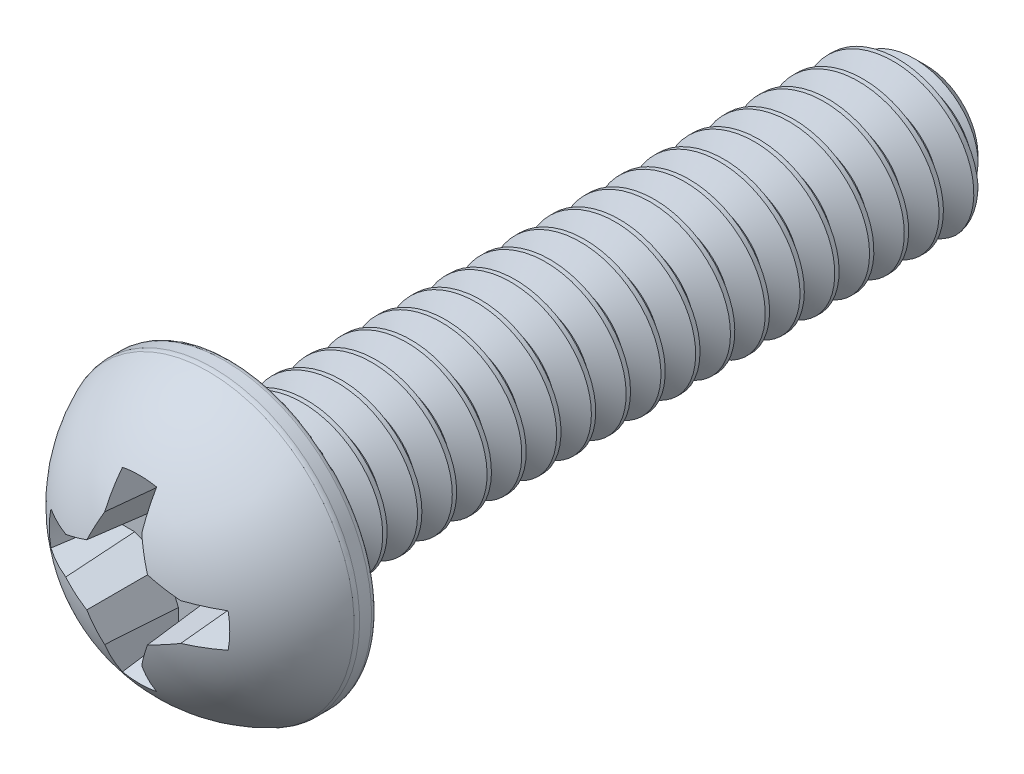
SolidWorks part; units mm, degrees
ref_plane "Front" through (0, 0, 0) normal (0, 0, 1) x (1, 0, 0)
ref_plane "Top" through (0, 0, 0) normal (0, 1, 0) x (1, 0, 0)
ref_plane "Right" through (0, 0, 0) normal (1, 0, 0) x (0, 0, -1)
sketch "Sketch1" plane through (0, 0, 0) normal (0, 0, 1) x (1, 0, 0)
  circle A0 centre (0, 0) radius 2.6797
  dimension "Head Dia" = 5.3594
extrude "Extrude3" add sketch "Sketch1" along normal blind 2.1844
sketch "Sketch11" plane through (0, 0, 0) normal (1, 0, 0) x (0, 0, -1)
  line L0 (0, 0) -> (-2.4384, 0) construction
  line L4 (-2.1844, 2.6797) -> (-2.1844, -2.6797) construction
  line L5 (-2.4384, 3.1064) -> (0, 3.1064)
  line L7 (0, 3.1064) -> (0, 2.5705)
  line L8 (-0.3277, 2.6797) -> (-0.1092, 2.6797)
  line L9 (0, -2.6797) -> (0, 2.6797) construction
  line L11 (0, 2.6797) -> (-2.1844, 2.6797) construction
  line L13 (-2.1844, 0) -> (-2.4384, 0)
  line L14 (-2.4384, 0) -> (-2.4384, 3.1064)
  arc A0 (-0.412, 2.6628) -> (-2.1844, 0) centre (0.702, 0) ccw
  arc A1 (-0.1092, 2.6797) -> (0, 2.5705) centre (-0.1092, 2.5705) cw
  arc A2 (-0.412, 2.6628) -> (-0.3277, 2.6797) centre (-0.3277, 2.4613) cw
  dimension "D2" = 0.1092
  dimension "D4" = 0.2184
  dimension "D3" = 0.254
  dimension "D1" = 0.2184
  dimension "D5" = 0.5359
revolve "Cut-Revolve3" cut sketch "Sketch11" angle 360 about L0
sketch "Sketch4" plane through (0, 0, 0) normal (1, 0, 0) x (0, 0, -1)
  line L0 (0, 0) -> (12.7, 0)
  line L3 (12.7, 0) -> (12.7, 1.4224)
  line L4 (12.7, 1.4224) -> (0, 1.4224)
  line L6 (0, 1.4224) -> (0, 0)
  line L9 (12.7, 1.4224) -> (12.7, -1.4224) construction
  dimension "length" = 12.7
  dimension "dia" = 2.8448
revolve "Revolve1" add sketch "Sketch4" angle 360 about L0
chamfer "Chamfer1" distance 0.4763 angle 45 1 edges at (1.4224, 0, -12.7)
sketch "Sketch13" plane through (0, 0, -12.7) normal (0, 0, -1) x (-1, 0, 0)
  circle A2 centre (0, 0) radius 1.4224
curve "Helix/Spiral1" pitch 0.635 height 14.605 turns 23
sketch "Sketch14" plane through (0, 0, 0) normal (1, 0, 0) x (0, 0, -1)
  line L0 (12.7, 1.4224) -> (13.2556, 1.4224)
  line L1 (13.2556, 1.4224) -> (13.0175, 0.9928)
  line L2 (13.0175, 0.9928) -> (12.9381, 0.9928)
  line L3 (12.9381, 0.9928) -> (12.7, 1.4224)
  line L4 (12.8191, 1.2076) -> (13.1366, 1.2076) construction
  dimension "D1" = 0.0794
  dimension "D2" = 58
  dimension "D3" = 0.3175
sweep "Cut-Sweep1" cut profiles "Sketch14" path "Helix/Spiral1"
ref_plane "Plane1" through (0, 0, 25.4) normal (0, 0, -1) x (-1, 0, 0)
sketch "Sketch29" [suppressed] plane through (0, 0, -38.1) normal (0, 0, -1) x (-1, 0, 0)
  circle A0 centre (0, 0) radius 4.7625 construction
  circle A1 centre (0, 0) radius 4.7625
  point P3 (0, -4.7625)
extrude "Extrude11" [suppressed] add sketch "Sketch29" against normal up to surface (38.1 mm away)
sketch "Sketch26" plane through (0, 0, 0) normal (0, 0, 1) x (1, 0, 0)
  circle A1 centre (0, 0) radius 0.5461
  dimension "D1" = 1.0922
extrude "Extrude8" add sketch "Sketch26" along normal up to surface (2.1323 mm away)
ref_plane "Plane2" through (0, 0, 2.1844) normal (0, 0, 1) x (1, 0, 0)
sketch "Sketch12" plane through (0, 0, 2.1844) normal (0, 0, 1) x (1, 0, 0)
  line L0 (0, 0) -> (0.3573, 0.3573) construction
  line L1 (0, 0) -> (0, -1.1128) construction
  line L2 (1.7504, 0.3573) -> (1.0538, 0.3573)
  line L3 (0, 1.7865) -> (0, 2.6797) construction
  line L8 (0.3573, 1.0538) -> (0.3573, 1.7504)
  line L9 (0.3573, 0.3573) -> (1.0538, 1.0538) construction
  line L10 (1.0538, 0.3573) -> (0.5613, 0.5613)
  line L11 (0.5613, 0.5613) -> (0.3573, 1.0538)
  line L12 (1.0538, 0.3573) -> (0.3573, 0.3573) construction
  line L13 (0.3573, 1.0538) -> (0.3573, 0.3573) construction
  line L14 (0, 0) -> (0, 1.7865)
  line L15 (0, 0) -> (1.7865, 0)
  circle A1 centre (0, 0) radius 2.6797 construction
  arc A2 (1.7865, 0) -> (1.7504, 0.3573) centre (0, 0) ccw
  arc A3 (0.3573, 1.7504) -> (0, 1.7865) centre (0, 0) ccw
  circle A5 centre (0, 0) radius 1.1128 construction
  arc A6 (1.0538, 0.3573) -> (0.3573, 1.0538) centre (1.0538, 1.0538) cw construction
  dimension "Phillips Dia" = 3.5729
  dimension "Phillips Width" = 0.7146
  dimension "D1" = 0.8932
extrude "Cut-Extrude3" cut sketch "Sketch12" against normal blind 1.4563
pattern_circular "CirPattern1" count 4 over 360 about axis through (0, 0, 0) along (0, 0, 1) of "Cut-Extrude3"
draft "Draft1" type of draft neutral plane draft angle 15 neutral plane "Plane2" faces to draft 4 face at (-1.7684, 0, 1.1466) face at (0, -1.7684, 1.1466) face at (1.7684, 0, 1.1466) face at (0, 1.7684, 1.1466) neutral plane through (0, 0, 2.1844) neutral plane normal (0, 0, 1) parameters "D1"=15
draft "Draft2" type of draft neutral plane draft angle 5 neutral plane "Plane2" faces to draft 16 face at (0.3573, 1.2362, 1.1577) face at (0.459, 0.8082, 1.3759) face at (0.8082, 0.459, 1.3759) face at (1.2362, 0.3573, 1.1577) face at (1.2362, -0.3573, 1.1577) face at (0.8082, -0.459, 1.3759) face at (0.459, -0.8082, 1.3759) face at (0.3573, -1.2362, 1.1577) face at (-0.3573, -1.2362, 1.1577) face at (-0.459, -0.8082, 1.3759) face at (-0.8082, -0.459, 1.3759) face at (-1.2362, -0.3573, 1.1577) face at (-1.2362, 0.3573, 1.1577) face at (-0.8082, 0.459, 1.3759) face at (-0.459, 0.8082, 1.3759) face at (-0.3573, 1.2362, 1.1577) neutral plane through (0, 0, 2.1844) neutral plane normal (0, 0, 1) parameters "D1"=5
sketch "Sketch18" plane through (0, 0, 0) normal (1, 0, 0) x (0, 0, -1)
  line L1 (12.7, 1.4224) -> (0, 1.4224) construction
  point P0 (11.7475, -1.4224)
  point P1 (12.065, 1.4224)
  point P2 (-2.1844, 0.5613)
  dimension "D1" = 0.635
  dimension "D2" = 0.9525
equation "\"Phillips Dia@Sketch12\"=\"Head Dia@Sketch1\"/1.5"
equation "\"Phillips Width@Sketch12\"=\"Phillips Dia@Sketch12\"/5"
equation "\"Phillips Depth@Cut-Extrude3\"= \"Head Ht@Extrude3\" / 1.5"
equation "\"D3@Helix/Spiral1\" = \"length@Sketch4\" + \"D4@Helix/Spiral1\" + .05"
equation "\"D1@Sketch14\" = \"D4@Helix/Spiral1\" * .125"
equation "\"D3@Sketch14\" = \"D4@Helix/Spiral1\" * .5"
equation "\"D1@Sketch11\" = \"Head Ht@Extrude3\" / 10"
equation "\"D2@Sketch11\" = \"D1@Sketch11\" / 2"
equation "\"D4@Sketch11\" = \"D1@Sketch11\""
equation "\"D5@Sketch11\" = \"Head Dia@Sketch1\" / 10"
equation "\"D1@Chamfer1\" = \"D4@Helix/Spiral1\" * .75"
equation "\"D1@Sketch18\" = \"D4@Helix/Spiral1\""
equation "\"D2@Sketch18\" = \"D4@Helix/Spiral1\" * 1.5"
